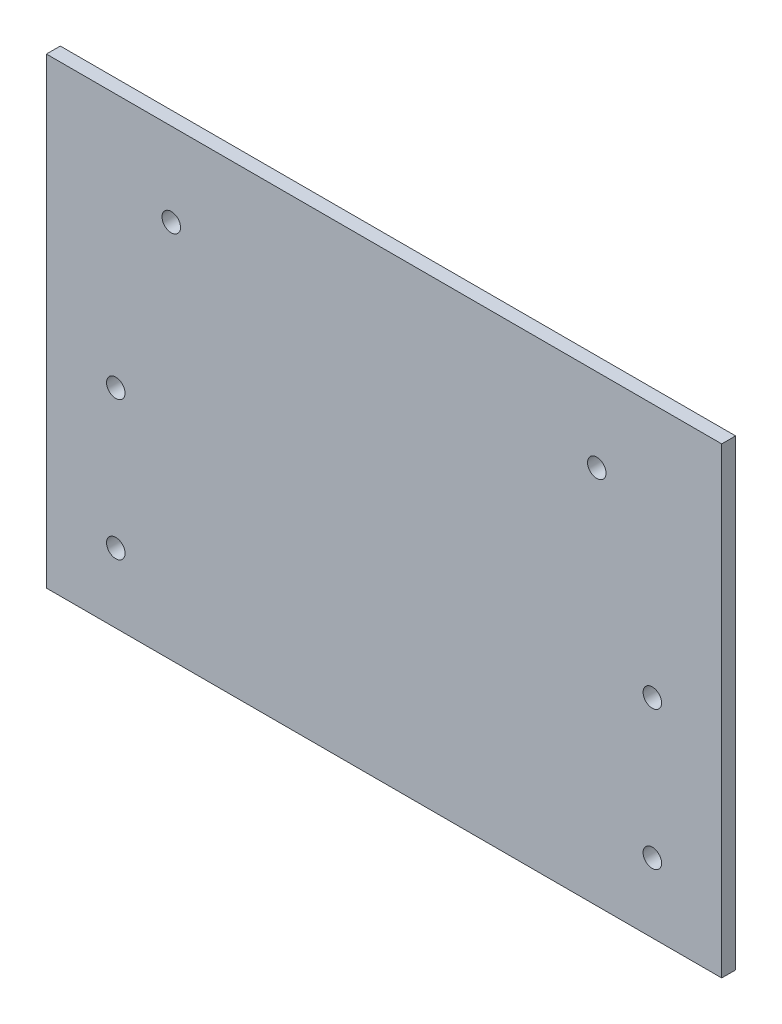
SolidWorks part; units mm, degrees
ref_plane "Front Plane" through (0, 0, 0) normal (0, 0, 1) x (1, 0, 0)
ref_plane "Top Plane" through (0, 0, 0) normal (0, 1, 0) x (1, 0, 0)
ref_plane "Right Plane" through (0, 0, 0) normal (1, 0, 0) x (0, 0, -1)
sketch "Sketch1" plane through (0, 0, 0) normal (0, 0, 1) x (1, 0, 0)
  line L1 (-74.1235, 86.0212) -> (71.8765, 86.0212)
  line L2 (-74.1235, 86.0212) -> (-74.1235, -13.9788)
  line L3 (-74.1235, -13.9788) -> (71.8765, -13.9788)
  line L4 (71.8765, 86.0212) -> (71.8765, -13.9788)
  dimension "D1" = 146
  dimension "D2" = 100
extrude "Boss-Extrude1" add sketch "Sketch1" along normal blind 3
sketch "Sketch2" plane through (0, 0, 0) normal (0, 0, -1) x (-1, 0, 0)
  circle A0 centre (59.1235, 1.0212) radius 2
  circle A1 centre (-56.8765, 1.0212) radius 2
  dimension "D1" = 4
  dimension "D2" = 4
extrude "Cut-Extrude1" cut sketch "Sketch2" against normal through all
sketch "Sketch3" plane through (0, 0, 0) normal (0, 0, -1) x (-1, 0, 0)
  circle A0 centre (-56.8765, 31.0212) radius 2
  circle A1 centre (59.1235, 31.0212) radius 2
  dimension "D1" = 4
extrude "Cut-Extrude2" cut sketch "Sketch3" against normal through all
sketch "Sketch4" plane through (0, 0, 0) normal (0, 0, -1) x (-1, 0, 0)
  circle A0 centre (-44.8668, 68.0399) radius 2
  circle A1 centre (47.1242, 68.0399) radius 2
  dimension "D1" = 4
  dimension "D2" = 4
extrude "Cut-Extrude3" cut sketch "Sketch4" against normal through all
